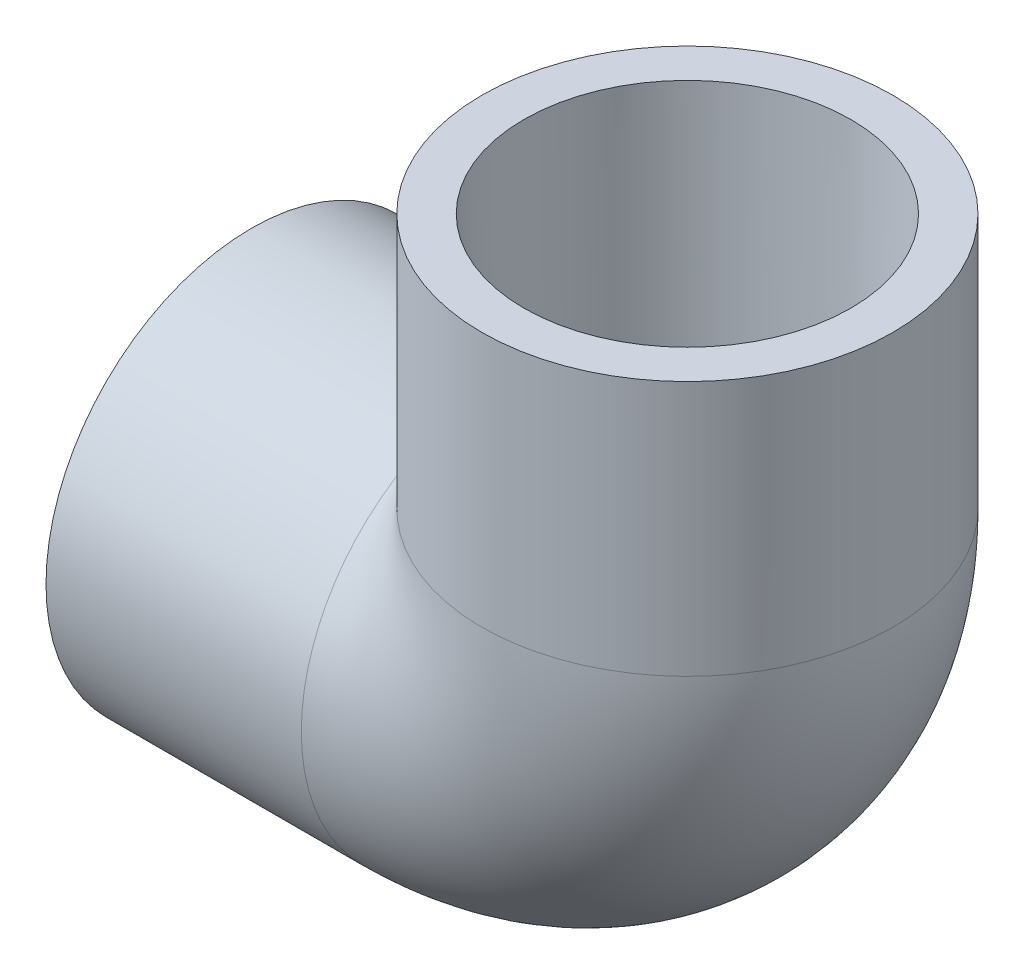
SolidWorks part; units mm, degrees
ref_plane "Front Plane" through (0, 0, 0) normal (0, 0, 1) x (1, 0, 0)
ref_plane "Top Plane" through (0, 0, 0) normal (0, 1, 0) x (1, 0, 0)
ref_plane "Right Plane" through (0, 0, 0) normal (1, 0, 0) x (0, 0, -1)
sketch "Sketch0" plane through (0, 0, 0) normal (0, 0, 1) x (1, 0, 0)
  line L0 (-35.56, 0) -> (0, 0) construction
  line L1 (0, 0) -> (0, 35.56) construction
  line L2 (-15.494, 0) -> (0, 0) construction
  line L3 (0, 0) -> (0, 14.732) construction
  line L4 (-35.56, 16.764) -> (-35.56, -16.764) construction
  line L5 (-15.494, 13.2842) -> (-35.56, 13.4366) construction
  line L6 (-15.494, 13.2842) -> (-15.494, -13.2842) construction
  line L7 (-15.494, -13.2842) -> (-35.56, -13.4366) construction
  line L8 (-35.56, 13.4366) -> (-35.56, -13.4366) construction
  line L9 (-16.764, 35.56) -> (16.764, 35.56) construction
  line L10 (-13.335, 35.56) -> (13.335, 35.56) construction
  line L11 (13.335, 35.56) -> (12.6865, 14.732) construction
  line L12 (12.6865, 14.732) -> (-12.6865, 14.732) construction
  line L13 (10.4648, 35.56) -> (9.8163, 14.732) construction
  line L14 (-15.494, -10.4648) -> (-15.494, 10.4648) construction
  line L15 (-10.4648, 35.56) -> (10.4648, 35.56) construction
  line L17 (-12.9034, 21.6992) -> (12.9034, 21.6992) construction
  line L18 (-9.8163, 14.732) -> (9.8163, 14.732) construction
  point P26 (0, 21.6992)
  point P27 (-14.732, 0)
  dimension "D1" = 14.732
  dimension "D2" = 14.732
sketch "Sketch1" plane through (0, 0, 0) normal (0, 0, 1) x (1, 0, 0)
  line L0 (-35.56, 0) -> (0, 0) construction
  line L1 (-35.56, 0) -> (0, 0) construction
  line L2 (-14.732, -12.6873) -> (-14.732, -16.764)
  line L3 (-14.732, -16.764) -> (-35.56, -16.764)
  line L4 (-35.56, -16.764) -> (-35.56, -13.335)
  line L5 (-35.56, -13.335) -> (-14.732, -12.6873)
  line L8 (-14.732, -10.4648) -> (-14.732, 0) construction
  dimension "D1" = 0
  dimension "D2" = 20.828
  dimension "D3" = 3.429
  dimension "D4" = 4.0767
  dimension "D5" = 16.764
revolve "Revolve1" add sketch "Sketch1" angle 360 about L1
sketch "Sketch2" plane through (0, 0, 0) normal (0, 0, 1) x (1, 0, 0)
  line L0 (13.335, 35.56) -> (12.6865, 14.732)
  line L1 (12.6865, 14.732) -> (16.764, 14.732)
  line L2 (16.764, 14.732) -> (16.764, 35.56)
  line L3 (16.764, 35.56) -> (13.335, 35.56)
  line L4 (0, 0) -> (0, 35.56) construction
  line L5 (0, 0) -> (0, 35.56) construction
revolve "Revolve2" add sketch "Sketch2" angle 360 about L5
sketch "Sketch3" plane through (-14.732, 0, 0) normal (1, 0, 0) x (0, 0, -1)
  circle A0 centre (0, 0) radius 12.6873
  circle A1 centre (0, 0) radius 16.764
sketch "Sketch4" plane through (0, 0, 0) normal (0, 0, 1) x (1, 0, 0)
  line L0 (-35.56, 0) -> (0, 0) construction
  line L1 (0, 0) -> (0, 35.56) construction
  line L2 (-35.56, 0) -> (-14.732, 0) construction
  line L3 (0, 14.732) -> (0, 35.56) construction
  arc A0 (-14.732, 0) -> (0, 14.732) centre (-14.732, 14.732) ccw
sweep "Sweep1" add profiles "Sketch3" path "Sketch4"
sketch "Sketch5" plane through (0, 35.56, 0) normal (0, 1, 0) x (1, 0, 0)
  circle A0 centre (0, 0) radius 13.335 construction
  circle A1 centre (0, 0) radius 13.335
  point P3 (-13.335, 0)
curve "Helix/Spiral1" parameters "Height"=22.6423, "Pitch"=1.8143
sketch "SketchX" [suppressed] plane through (0, 0, 0) normal (0, 0, 1) x (1, 0, 0)
  line L0 (-15.494, 13.2842) -> (-35.56, 13.4366) construction
  line L1 (-35.56, -13.4366) -> (-15.494, -13.2842) construction
  line L2 (-13.335, 35.56) -> (-12.6865, 14.732) construction
  line L3 (12.6865, 14.732) -> (13.335, 35.56) construction
  line L4 (-15.494, 13.2842) -> (-35.56, 13.4366)
  line L5 (-35.56, -13.4366) -> (-15.494, -13.2842)
  line L6 (-13.335, 35.56) -> (-12.6865, 14.732)
  line L7 (12.6865, 14.732) -> (13.335, 35.56)
  line L8 (-12.6865, 14.732) -> (12.6865, 14.732)
  line L9 (-15.494, 13.2842) -> (-15.494, -13.2842)
  arc A0 (-14.732, -10.4648) -> (10.4648, 14.732) centre (-14.732, 14.732) ccw construction
  arc A1 (-14.732, 10.4648) -> (-10.4648, 14.732) centre (-14.732, 14.732) ccw construction
  arc A2 (-14.732, -10.4648) -> (10.4648, 14.732) centre (-14.732, 14.732) ccw
  arc A3 (-14.732, 10.4648) -> (-10.4648, 14.732) centre (-14.732, 14.732) ccw
sketch "Sketch6" plane through (0, 0, 0) normal (0, 0, 1) x (1, 0, 0)
  line L0 (-13.5618, 37.2434) -> (-13.5618, 35.4291) construction
  line L1 (-13.5618, 35.4291) -> (-11.9906, 36.3362) construction
  line L2 (-11.9906, 36.3362) -> (-13.5618, 37.2434) construction
  line L3 (-13.335, 37.1124) -> (-13.335, 35.56) construction
  line L4 (-12.2174, 36.4671) -> (-12.2174, 36.2053) construction
  line L5 (-13.5618, 36.3362) -> (-13.335, 36.3362) construction
  line L6 (-12.2174, 36.3362) -> (-11.9906, 36.3362) construction
  line L7 (-12.4441, 36.5981) -> (-12.4441, 36.0743)
  line L8 (-12.4441, 36.3362) -> (-12.2174, 36.3362) construction
  line L9 (-13.4484, 36.3362) -> (-13.4484, 35.4945) construction
  line L10 (-13.4484, 35.4945) -> (-13.5618, 37.2434)
  line L11 (-13.5618, 37.2434) -> (-12.4441, 36.5981)
  line L12 (-13.4484, 35.4945) -> (-12.4441, 36.0743)
  dimension "D1" = 1.8143
  dimension "D2" = 0.2268
sweep "Sweep2" [suppressed] add profiles "Sketch6" path "Helix/Spiral1"
sketch "Sketch7" plane through (0, 35.56, 0) normal (0, 1, 0) x (1, 0, 0)
  line L0 (0, 13.5618) -> (0, 0) construction
  circle A0 centre (0, 0) radius 13.5618
extrude "Cut-Extrude1" [suppressed] cut sketch "Sketch7" against normal up to vertex draft 45 and the other way through all draft 45
equation "\"Height@Helix/Spiral1\" = \"Pitch@Helix/Spiral1\" + \"L4@Sketch0\""
equation "\"D1@Sketch6\" = \"Pitch@Helix/Spiral1\""
equation "\"D2@Sketch6\" = \"D1@Sketch6\" * 1 / 8"
